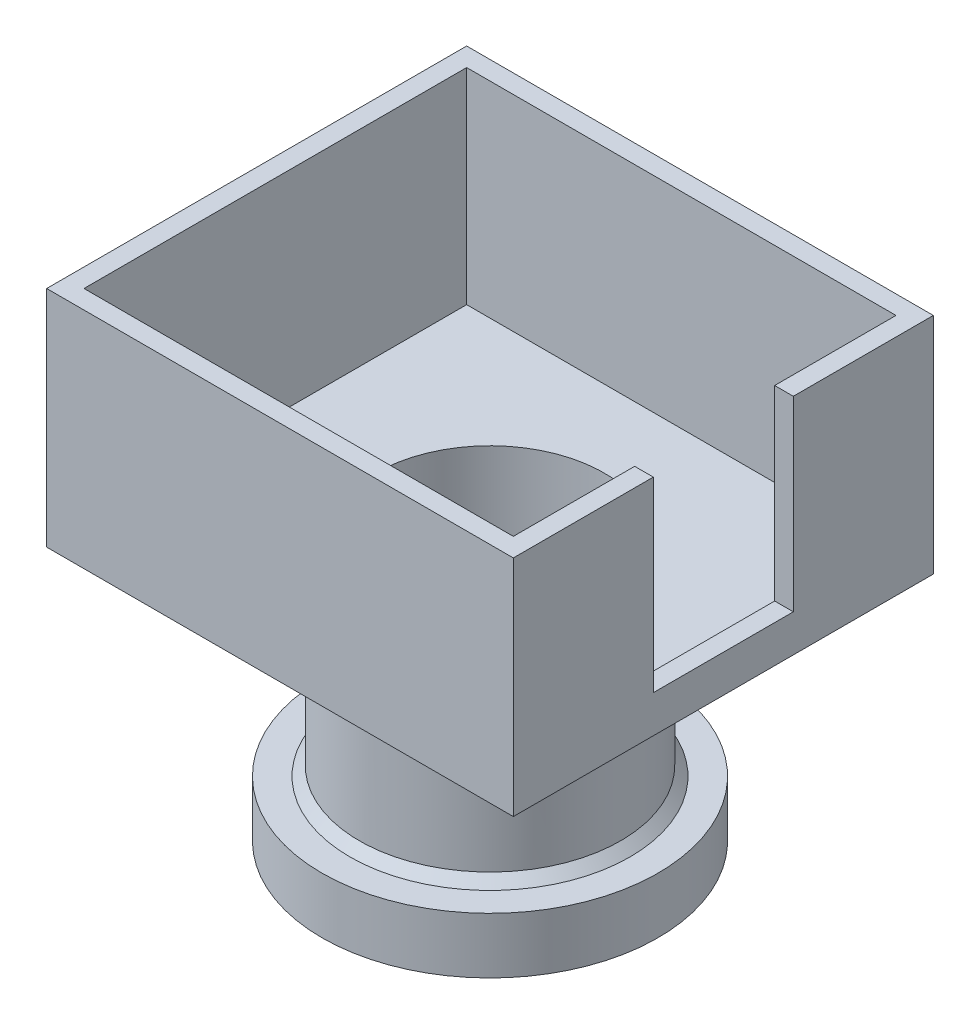
SolidWorks part; units mm, degrees
ref_plane "Front Plane" through (0, 0, 0) normal (0, 0, 1) x (1, 0, 0)
ref_plane "Top Plane" through (0, 0, 0) normal (0, 1, 0) x (1, 0, 0)
ref_plane "Right Plane" through (0, 0, 0) normal (1, 0, 0) x (0, 0, -1)
sketch "Sketch1" plane through (0, 0, 0) normal (0, 1, 0) x (1, 0, 0)
  line L7 (8.0829, -14) -> (16.1658, 0)
  line L8 (16.1658, 0) -> (8.0829, 14)
  line L9 (8.0829, 14) -> (-8.0829, 14)
  line L10 (-8.0829, 14) -> (-16.1658, 0)
  line L11 (-16.1658, 0) -> (-8.0829, -14)
  line L12 (-8.0829, -14) -> (8.0829, -14)
  circle A0 centre (0, 0) radius 14 construction
  circle A1 centre (0, 0) radius 18
  dimension "D2" = 36
  dimension "D1" = 28
extrude "Boss-Extrude1" add sketch "Sketch1" along normal blind 5
sketch "Sketch2" plane through (0, 5, 0) normal (0, 1, 0) x (1, 0, 0)
  circle A0 centre (0, 0) radius 12.25
  circle A1 centre (0, 0) radius 14
  dimension "D1" = 24.5
  dimension "D2" = 28
extrude "Boss-Extrude2" add sketch "Sketch2" along normal blind 21 separate body
sketch "Sketch3" plane through (0, 5, 0) normal (0, 1, 0) x (1, 0, 0)
  circle A0 centre (0, 0) radius 18 construction
  circle A1 centre (0, 0) radius 18
  circle A2 centre (0, 0) radius 12.25 construction
  circle A3 centre (0, 0) radius 12.25
extrude "Boss-Extrude3" add sketch "Sketch3" along normal blind 1
chamfer "Chamfer1" distance 1 angle 45 1 edges at (0, 6, 14)
sketch "Sketch4" plane through (0, 26, 0) normal (0, 1, 0) x (1, 0, 0)
  line L0 (0, 22.5) -> (0, -22.5) construction
  line L1 (-25, 22.5) -> (25, 22.5)
  line L2 (-25, 22.5) -> (-25, -22.5)
  line L3 (-25, -22.5) -> (25, -22.5)
  line L4 (25, 22.5) -> (25, -22.5)
  line L5 (-25, 0) -> (25, 0) construction
  circle A0 centre (0, 0) radius 12.25 construction
  circle A1 centre (0, 0) radius 12.25
  dimension "D1" = 45
  dimension "D2" = 50
extrude "Boss-Extrude4" add sketch "Sketch4" along normal blind 2
sketch "Sketch5" plane through (0, 28, 0) normal (0, 1, 0) x (1, 0, 0)
  line L0 (23, 20.5) -> (-23, 20.5)
  line L1 (-23, 20.5) -> (-23, -20.5)
  line L2 (-23, -20.5) -> (23, -20.5)
  line L3 (23, -20.5) -> (23, 20.5)
  line L4 (-25, 22.5) -> (-25, -22.5)
  line L5 (-25, -22.5) -> (25, -22.5)
  line L6 (25, -22.5) -> (25, 22.5)
  line L7 (25, 22.5) -> (-25, 22.5)
  line L8 (-25, 22.5) -> (-25, -22.5)
  line L9 (-25, -22.5) -> (25, -22.5)
  line L10 (25, -22.5) -> (25, 22.5)
  line L11 (25, 22.5) -> (-25, 22.5)
  dimension "D1" = 0
  dimension "D2" = 2
extrude "Boss-Extrude5" add sketch "Sketch5" along normal blind 22
chamfer "Chamfer2" distance 5 angle 45 1 edges at (0, 26, 14)
sketch "Sketch6" plane through (25, 0, 0) normal (1, 0, 0) x (0, 0, -1)
  line L0 (-22.5, 50) -> (22.5, 50) construction
  line L1 (-7.5, 50) -> (7.5, 50)
  line L2 (-7.5, 50) -> (-7.5, 30)
  line L3 (-7.5, 30) -> (7.5, 30)
  line L4 (7.5, 50) -> (7.5, 30)
  line L5 (0, 26) -> (0, 50) construction
  line L6 (-19, 26) -> (19, 26) construction
  dimension "D1" = 20
  dimension "D2" = 15
extrude "Cut-Extrude1" cut sketch "Sketch6" against normal blind 20
